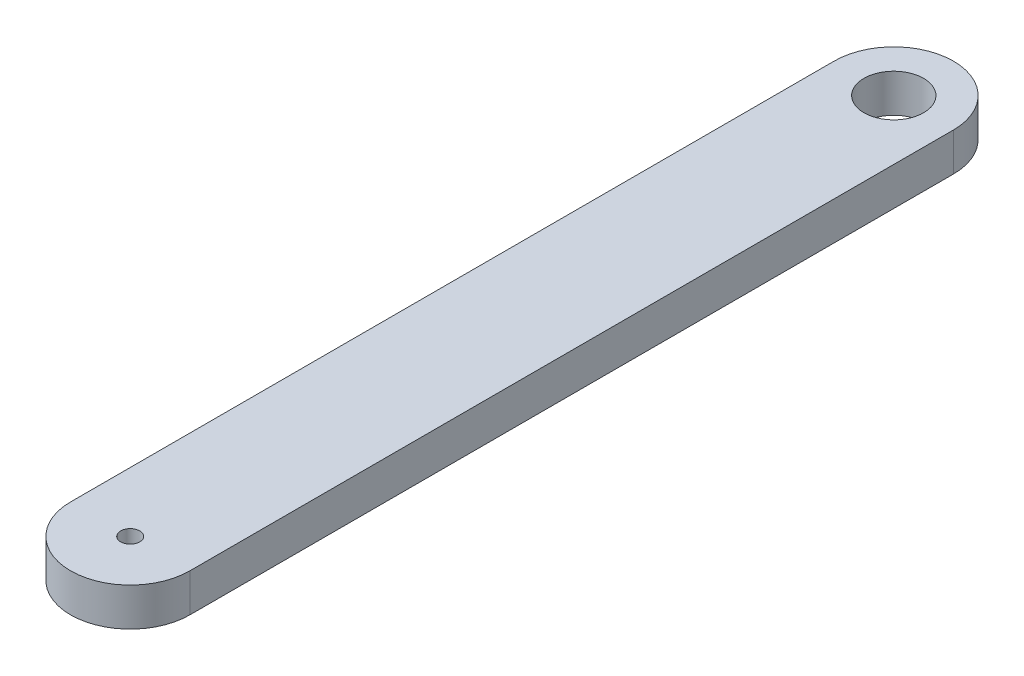
SolidWorks part; units mm, degrees
ref_plane "Front Plane" through (0, 0, 0) normal (0, 0, 1) x (1, 0, 0)
ref_plane "Top Plane" through (0, 0, 0) normal (0, 1, 0) x (1, 0, 0)
ref_plane "Right Plane" through (0, 0, 0) normal (1, 0, 0) x (0, 0, -1)
sketch "Sketch1" plane through (0, 0, 0) normal (0, 1, 0) x (1, 0, 0)
  line L0 (0, 0) -> (0, 160) construction
  line L1 (0, 80) -> (-25.4869, 80) construction
  line L2 (12.5, 160) -> (12.5, 0)
  line L3 (-12.5, 160) -> (-12.5, 0)
  circle A0 centre (0, 0) radius 2
  circle A1 centre (0, 0) radius 12.5
  circle A2 centre (0, 160) radius 12.5
  circle A3 centre (0, 160) radius 6.25
  dimension "D2" = 12.5
  dimension "D3" = 4
  dimension "D4" = 25
  dimension "D1" = 160
  dimension "D5" = 25
extrude "Boss-Extrude1" add sketch "Sketch1" along normal blind 8 contours A2 L3 A1 L2 | A2 A3 | A1 region at (0, 0, -147.8536) region at (0, 0, -80) region at (0, 0, 12.1464)
